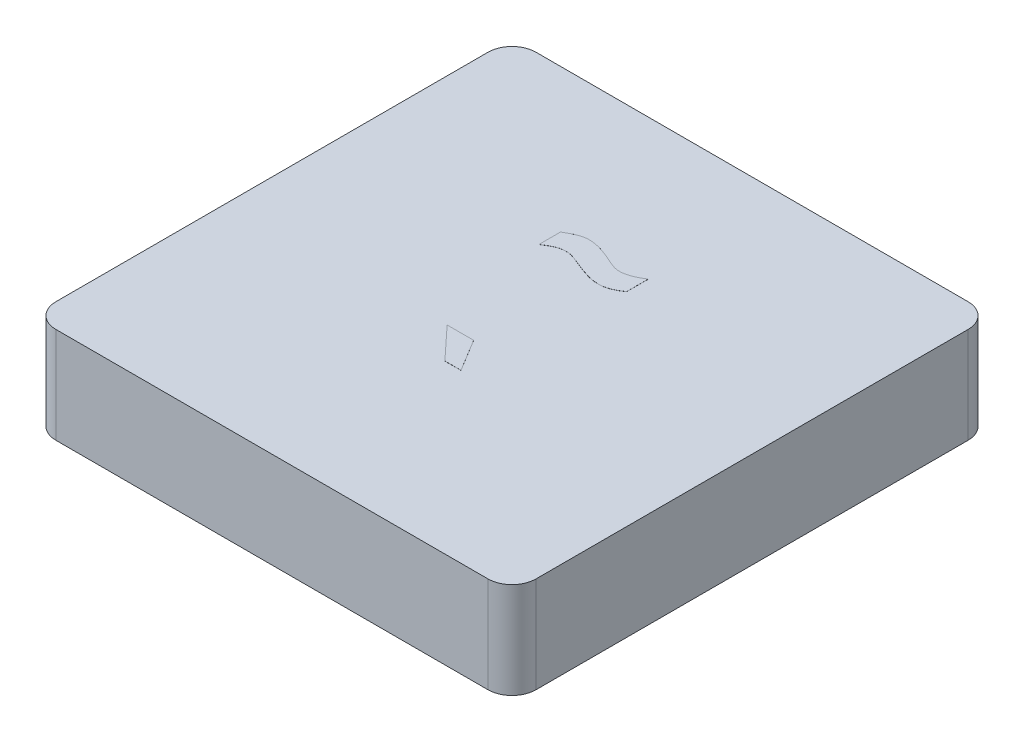
SolidWorks part; units mm, degrees
ref_plane "Front Plane" through (0, 0, 0) normal (0, 0, 1) x (1, 0, 0)
ref_plane "Top Plane" through (0, 0, 0) normal (0, 1, 0) x (1, 0, 0)
ref_plane "Right Plane" through (0, 0, 0) normal (1, 0, 0) x (0, 0, -1)
sketch "Sketch1" plane through (0, 0, 0) normal (0, 1, 0) x (1, 0, 0)
  line L0 (0, 0) -> (12.7, 0)
  line L1 (12.7, 0) -> (12.7, 12.7)
  line L2 (12.7, 12.7) -> (0, 12.7)
  line L3 (0, 12.7) -> (0, 0)
  dimension "D1" = 12.7
  dimension "D2" = 12.7
extrude "Boss-Extrude1" add sketch "Sketch1" along normal blind 2.54
fillet "Fillet1" radius 0.635 4 edges at (0, 1.27, -12.7) (12.7, 1.27, -12.7) (12.7, 1.27, 0) (0, 1.27, 0)
shell "Shell1" thickness 0.635 removed face at (6.35, 0, -6.35)
sketch "Sketch2" plane through (0, 1.905, 0) normal (0, -1, 0) x (-1, 0, 0)
  line L0 (-0.635, 6.35) -> (-12.065, 6.35) construction
  line L1 (-0.635, 12.065) -> (-0.635, 0.635) construction
  line L2 (-12.065, 0.635) -> (-12.065, 12.065) construction
  line L3 (-6.35, 0.635) -> (-6.35, 12.065) construction
  line L4 (-0.635, 0.635) -> (-12.065, 0.635) construction
  line L5 (-12.065, 12.065) -> (-0.635, 12.065) construction
  circle A0 centre (-6.35, 6.35) radius 2.54
  dimension "D1" = 5.08
extrude "Boss-Extrude2" add sketch "Sketch2" along normal up to surface (1.905 mm away) up to face at (6.35, 0, -6.35)
sketch "Sketch3" plane through (0, 2.54, 0) normal (0, 1, 0) x (1, 0, 0)
  line L0 (0, 12.065) -> (0, 0.635) construction
  line L1 (12.065, 12.7) -> (0.635, 12.7) construction
  line L2 (0.635, 0) -> (12.065, 0) construction
  text T0 "<b>`</b>"
  text T1 "<b>~</b>"
  dimension "D1" = 4.8768
  dimension "D2" = 5.588
  dimension "D3" = 5.588
  dimension "D4" = 1.651
extrude "Boss-Extrude3" add sketch "Sketch3" along normal blind 0.0025
